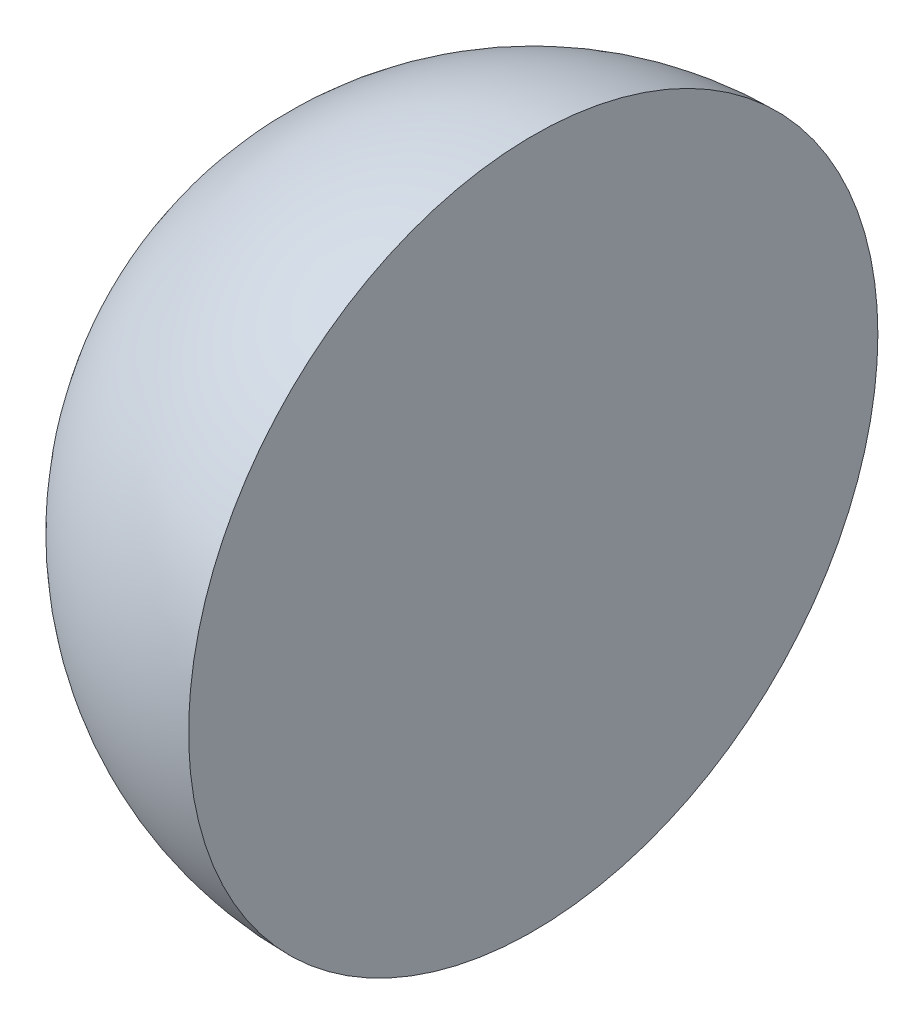
SolidWorks part; units mm, degrees
material "Polyurethane Foam Flexible"
ref_plane "Front Plane" through (0, 0, 0) normal (0, 0, 1) x (1, 0, 0)
ref_plane "Top Plane" through (0, 0, 0) normal (0, 1, 0) x (1, 0, 0)
ref_plane "Right Plane" through (0, 0, 0) normal (1, 0, 0) x (0, 0, -1)
sketch "Sketch1" plane through (0, 0, 0) normal (0, 0, 1) x (1, 0, 0)
  line L0 (0, 153.1806) -> (0, -37.3194) construction
  line L1 (0, 153.1806) -> (0, -37.3194)
  arc A0 (0, 153.1806) -> (0, -37.3194) centre (0, 57.9306) cw
revolve "Revolve1" add sketch "Sketch1" angle 360 about L0
sketch "Sketch2" plane through (0, 0, 0) normal (1, 0, 0) x (0, 0, -1)
  line L1 (-147.6601, 164.0257) -> (147.6601, 164.0257)
  line L2 (-147.6601, 164.0257) -> (-147.6601, -164.0257)
  line L3 (-147.6601, -164.0257) -> (147.6601, -164.0257)
  line L4 (147.6601, 164.0257) -> (147.6601, -164.0257)
  line L5 (-147.6601, 164.0257) -> (147.6601, -164.0257) construction
  line L6 (-147.6601, -164.0257) -> (147.6601, 164.0257) construction
  point P0 (0, 0)
extrude "Cut-Extrude1" cut sketch "Sketch2" along normal blind 95.25
